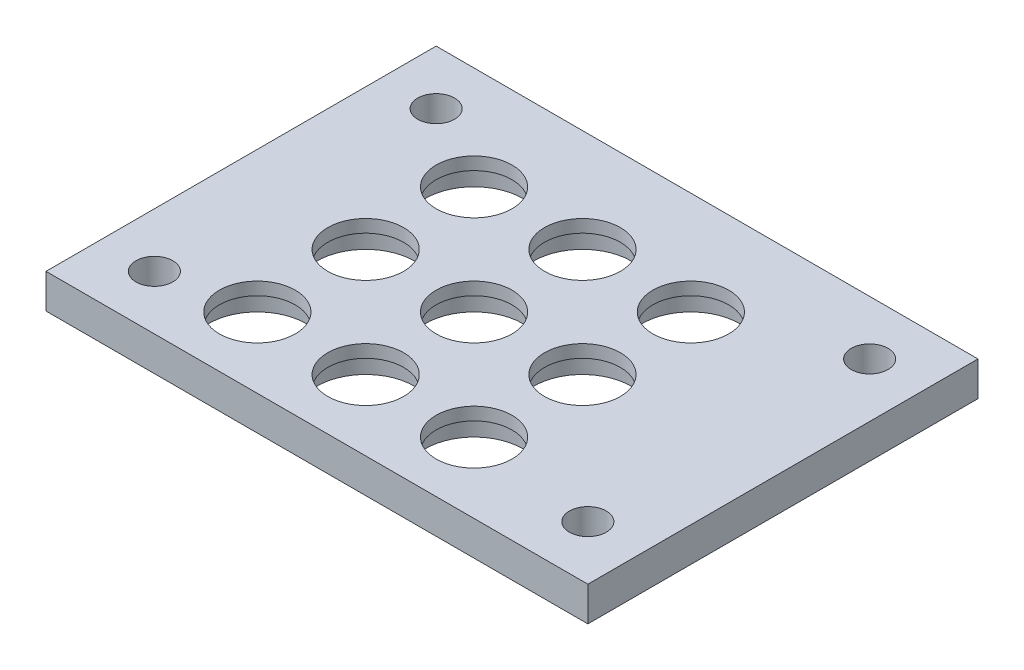
SolidWorks part; units mm, degrees
ref_plane "Front Plane" through (0, 0, 0) normal (0, 0, 1) x (1, 0, 0)
ref_plane "Top Plane" through (0, 0, 0) normal (0, 1, 0) x (1, 0, 0)
ref_plane "Right Plane" through (0, 0, 0) normal (1, 0, 0) x (0, 0, -1)
sketch "Sketch1" plane through (0, 0, 0) normal (0, 1, 0) x (1, 0, 0)
  line L0 (45, 31) -> (5, 31) construction
  line L1 (0, 0) -> (50, 0)
  line L2 (0, 0) -> (0, 36)
  line L3 (0, 36) -> (50, 36)
  line L4 (50, 0) -> (50, 36)
  line L6 (45, 31) -> (45, 5) construction
  circle A19 centre (13, 6.5) radius 3.5
  circle A28 centre (5, 5) radius 1.7
  circle A29 centre (5, 31) radius 1.7
  circle A30 centre (45, 31) radius 1.7
  circle A31 centre (45, 5) radius 1.7
  circle A32 centre (23, 6.5) radius 3.5
  circle A33 centre (33, 6.5) radius 3.5
  circle A34 centre (23, 16.5) radius 3.5
  circle A35 centre (33, 16.5) radius 3.5
  circle A36 centre (23, 26.5) radius 3.5
  circle A37 centre (33, 26.5) radius 3.5
  circle A38 centre (13, 16.5) radius 3.5
  circle A39 centre (13, 26.5) radius 3.5
  point P7 (45, 18)
  point P9 (25, 31)
  point P10 (25, 36)
  point P20 (50, 18)
  dimension "D5" = 40
  dimension "D6" = 26
  dimension "D3" = 7
  dimension "D8" = 3.4
  dimension "D1" = 50
  dimension "D2" = 36
  dimension "D4" = 8
  dimension "D7" = 1.5
  dimension "D9" = 3
extrude "Boss-Extrude1" add sketch "Sketch1" along normal blind 3.175 contours L1 L4 L3 L2 A39 A36 A34 region at (0.6161, 0, -18)
sketch "Sketch2" plane through (0, 0, 0) normal (0, -1, 0) x (1, 0, 0)
  circle A0 centre (13, -6.5) radius 4.5
  circle A1 centre (13, -6.5) radius 3.5 construction
  circle A2 centre (23, -6.5) radius 4.5
  circle A3 centre (33, -6.5) radius 4.5
  circle A4 centre (23, -16.5) radius 4.5
  circle A5 centre (33, -16.5) radius 4.5
  circle A6 centre (23, -26.5) radius 4.5
  circle A7 centre (33, -26.5) radius 4.5
  circle A8 centre (13, -16.5) radius 4.5
  circle A9 centre (13, -26.5) radius 4.5
  dimension "D1" = 9
  dimension "D2" = 3
  dimension "D3" = 3
extrude "Cut-Extrude1" cut sketch "Sketch2" against normal blind 2
equation "\"o\"= 10mm"
equation "\"P\"= 10"
